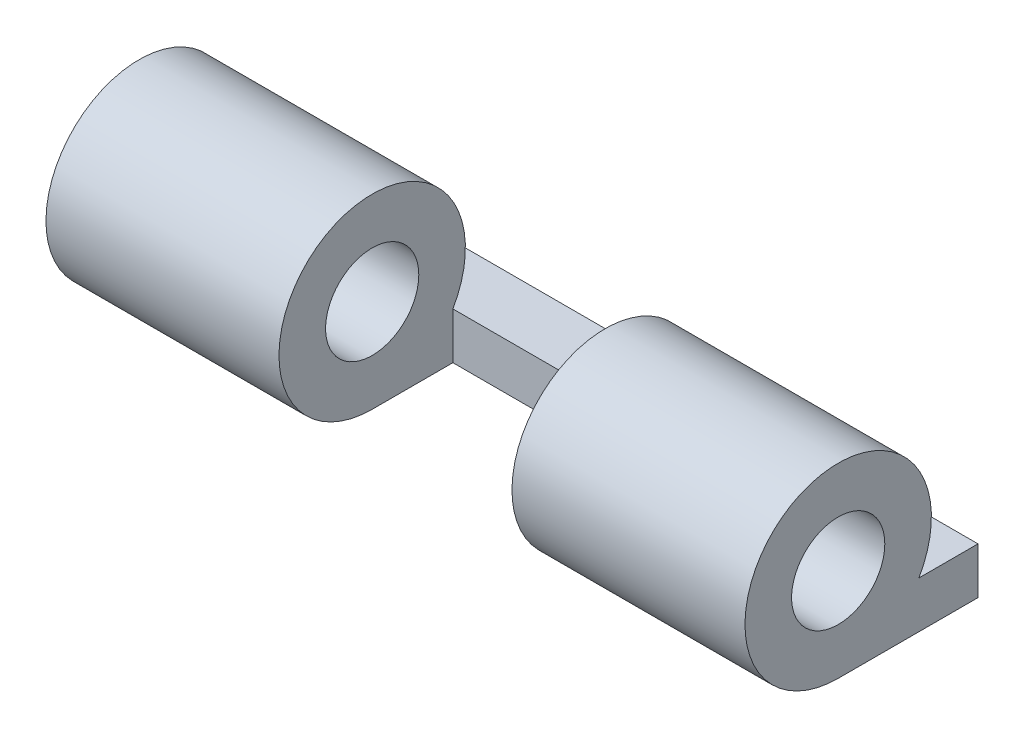
SolidWorks part; units mm, degrees
ref_plane "Ebene vorne" through (0, 0, 0) normal (0, 0, 1) x (1, 0, 0)
ref_plane "Ebene oben" through (0, 0, 0) normal (0, 1, 0) x (1, 0, 0)
ref_plane "Ebene rechts" through (0, 0, 0) normal (1, 0, 0) x (0, 0, -1)
sketch "Skizze1" plane through (0, 0, 0) normal (0, 1, 0) x (1, 0, 0)
  line L1 (0, 0) -> (15, 0)
  line L2 (0, 0) -> (0, 3)
  line L3 (0, 3) -> (15, 3)
  line L4 (15, 0) -> (15, 3)
  dimension "D1" = 15
  dimension "D2" = 3
extrude "Aufsatz-Linear austragen1" add sketch "Skizze1" along normal blind 1
sketch "Skizze2" plane through (15, 0, 0) normal (1, 0, 0) x (0, 0, -1)
  circle A0 centre (0, 2) radius 2
  circle A1 centre (0, 2) radius 1
  dimension "D1" = 2
  dimension "D2" = 1
extrude "Aufsatz-Linear austragen2" add sketch "Skizze2" against normal up to surface (15 mm away) up to face at (0, 0.5, -1.5)
ref_plane "Tangential Ebene" through (0, 0, -2) normal (0, 0, -1) x (-1, 0, 0)
sketch "Skizze8" plane through (15, 0, 0) normal (1, 0, 0) x (0, 0, -1)
  line L0 (1.7321, 1) -> (1.7321, 0)
  line L1 (1.7321, 0) -> (0, 0)
  line L3 (0, 0) -> (3, 0)
  line L4 (3, 0) -> (3, 1)
  line L5 (3, 1) -> (1.7321, 1)
  line L6 (0, 0) -> (3, 0) construction
  line L7 (3, 0) -> (3, 1) construction
  line L8 (3, 1) -> (1.7321, 1) construction
  arc A1 (1.7321, 1) -> (0, 0) centre (0, 2) ccw
  arc A2 (1.7321, 1) -> (0, 0) centre (0, 2) ccw
  dimension "D1" = 0
extrude "Schnitt-Linear austragen1" cut sketch "Skizze8" against normal blind 5 from offset 5 offset against normal yes
